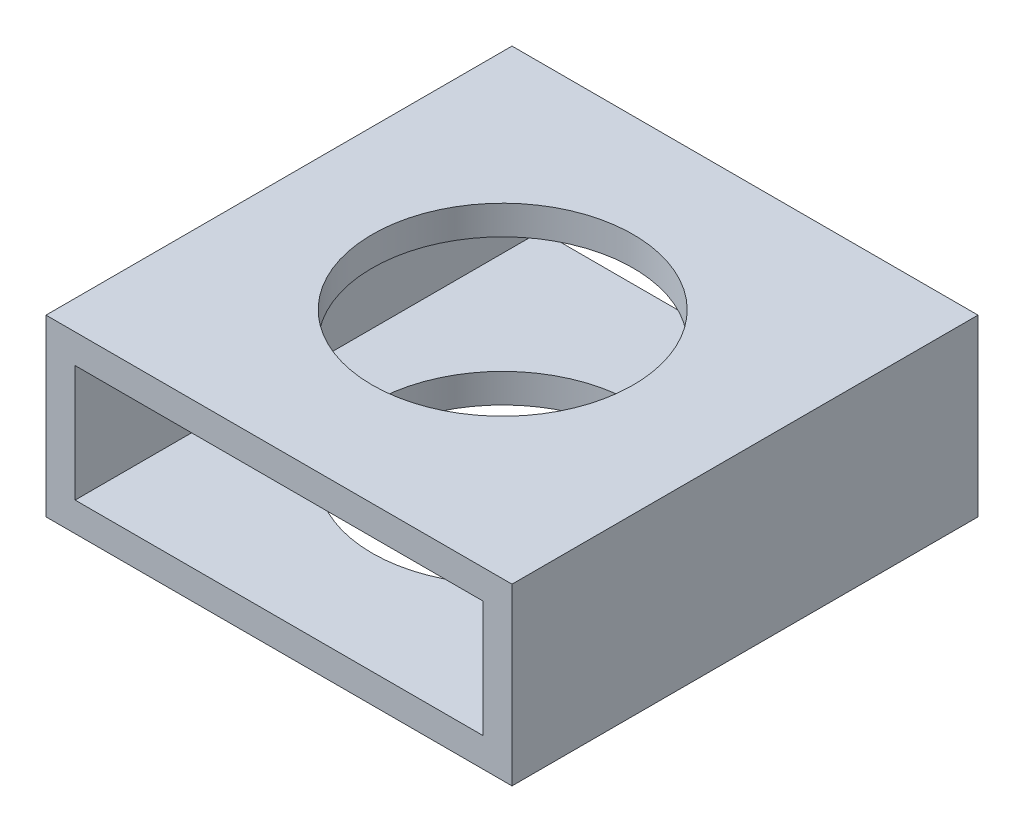
SolidWorks part; units mm, degrees
ref_plane "Front" through (0, 0, 0) normal (0, 0, 1) x (1, 0, 0)
ref_plane "Top" through (0, 0, 0) normal (0, 1, 0) x (1, 0, 0)
ref_plane "Right" through (0, 0, 0) normal (1, 0, 0) x (0, 0, -1)
sketch "Sketch1" plane through (0, 0, 0) normal (0, 0, 1) x (1, 0, 0)
  line L1 (-57.5643, 21.1125) -> (-6.7643, 21.1125)
  line L2 (-57.5643, 21.1125) -> (-57.5643, 2.0625)
  line L3 (-57.5643, 2.0625) -> (-6.7643, 2.0625)
  line L4 (-6.7643, 21.1125) -> (-6.7643, 2.0625)
  dimension "D1" = 50.8
  dimension "D2" = 19.05
extrude "Boss-Extrude1" add sketch "Sketch1" along normal blind 50.8
sketch "Sketch2" plane through (0, 0, 0) normal (0, 0, -1) x (-1, 0, 0)
  line L8 (54.3893, 5.2375) -> (54.3893, 17.9375)
  line L9 (54.3893, 17.9375) -> (9.9393, 17.9375)
  line L10 (9.9393, 17.9375) -> (9.9393, 5.2375)
  line L11 (9.9393, 5.2375) -> (54.3893, 5.2375)
  line L12 (54.3893, 5.2375) -> (54.3893, 17.9375)
  line L13 (54.3893, 17.9375) -> (9.9393, 17.9375)
  line L14 (9.9393, 17.9375) -> (9.9393, 5.2375)
  line L15 (9.9393, 5.2375) -> (54.3893, 5.2375)
  dimension "D1" = 3.175
extrude "Cut-Extrude1" cut sketch "Sketch2" against normal through all
sketch "Sketch5" plane through (0, 21.1125, 0) normal (0, 1, 0) x (1, 0, 0)
  line L1 (-6.7643, -50.8) -> (-6.7643, 0) construction
  line L2 (-6.7643, -25.4) -> (-33.1803, -25.4)
  circle A0 centre (-33.1803, -25.4) radius 14.224
extrude "Cut-Extrude2" cut sketch "Sketch5" against normal through all contours A0
